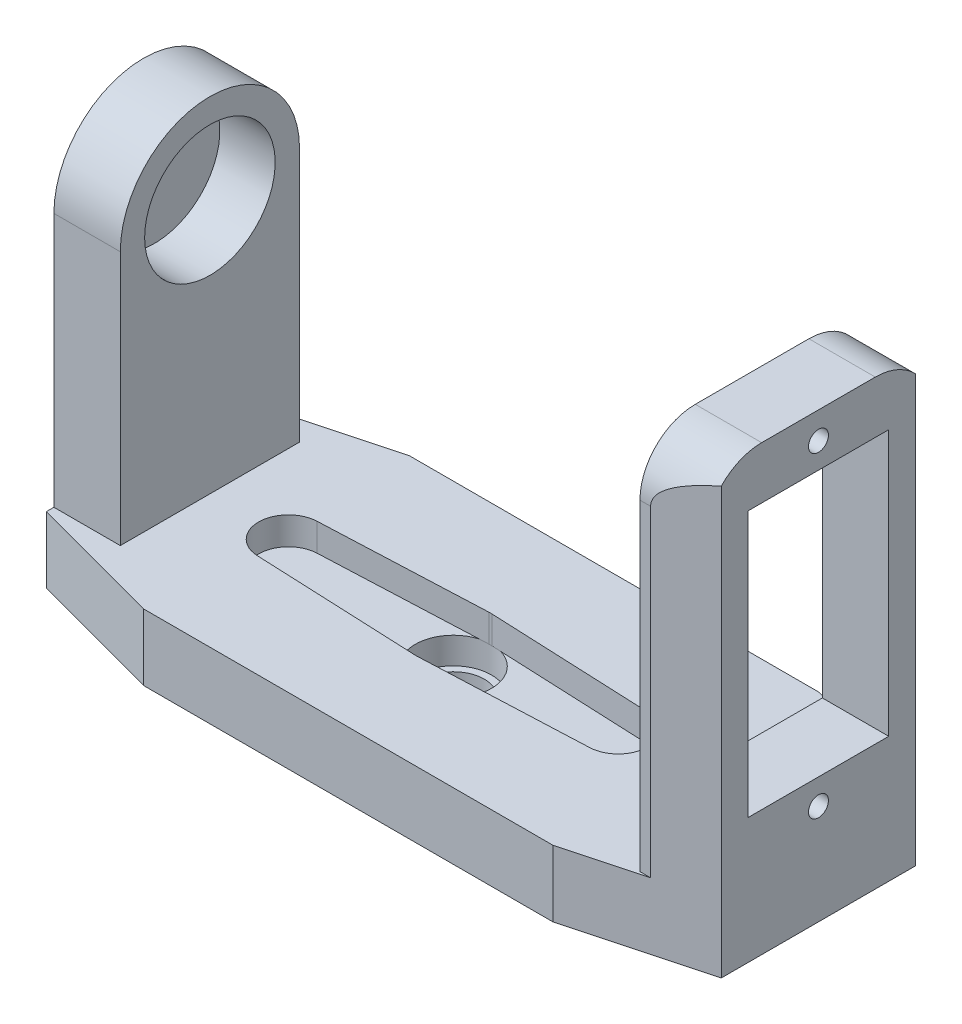
SolidWorks part; units mm, degrees
ref_plane "前视基准面" through (0, 0, 0) normal (0, 0, 1) x (1, 0, 0)
ref_plane "上视基准面" through (0, 0, 0) normal (0, 1, 0) x (1, 0, 0)
ref_plane "右视基准面" through (0, 0, 0) normal (1, 0, 0) x (0, 0, -1)
sketch "草图1" plane through (0, 0, 0) normal (0, 1, 0) x (1, 0, 0)
  line L0 (0, 0) -> (2.5, 0) construction
  line L1 (33, -12) -> (-28, -12)
  line L2 (33, -12) -> (33, 12)
  line L3 (33, 12) -> (-28, 12)
  line L4 (-28, -12) -> (-28, 12)
  line L5 (33, -12) -> (-28, 12) construction
  line L6 (33, 12) -> (-28, -12) construction
  point P0 (0, 0)
  dimension "D1" = 28
  dimension "D2" = 33
  dimension "D3" = 24
extrude "凸台-拉伸1" add sketch "草图1" along normal blind 6
sketch "草图2" plane through (-28, 0, 0) normal (-1, 0, 0) x (0, 0, 1)
  line L0 (-12, 6) -> (12, 6) construction
  line L1 (8.0991, 37.0991) -> (-8.0991, 37.0991)
  line L2 (8.0991, 37.0991) -> (8.0991, 6)
  line L3 (8.0991, 6) -> (-8.0991, 6)
  line L4 (-8.0991, 37.0991) -> (-8.0991, 6)
  line L5 (8.0991, 37.0991) -> (-8.0991, 6) construction
  line L6 (8.0991, 6) -> (-8.0991, 37.0991) construction
  line L7 (0, 21.5496) -> (0, 6) construction
  circle A0 centre (0, 29) radius 5.9
  circle A1 centre (0, 29) radius 8.0991 construction
  point P0 (0, 21.5496)
  dimension "D2" = 11.8
  dimension "D1" = 23
extrude "凸台-拉伸2" add sketch "草图2" against normal blind 6
sketch "草图8" plane through (-28, 0, 0) normal (-1, 0, 0) x (0, 0, 1)
  circle A1 centre (0, 29) radius 5.9 construction
  circle A2 centre (0, 29) radius 5.9
extrude "凸台-拉伸4" add sketch "草图8" against normal blind 1
fillet "圆角1" 2 edges at (-25, 37.0991, -8.0991) (-25, 37.0991, 8.0991) type full round first side face at (-25, 21.5496, -8.0991) second side face at (-25, 21.5496, 8.0991) middle face at (-25, 37.0991, 0)
sketch "草图3" plane through (33, 0, 0) normal (1, 0, 0) x (0, 0, -1)
  line L0 (0, 23.35) -> (18.2252, 23.35) construction
  line L1 (10.134, 40.0752) -> (-10.134, 40.0752)
  line L2 (10.134, 40.0752) -> (10.134, 6)
  line L3 (10.134, 6) -> (-10.134, 6)
  line L4 (-10.134, 40.0752) -> (-10.134, 6)
  line L5 (10.134, 40.0752) -> (-10.134, 6) construction
  line L6 (10.134, 6) -> (-10.134, 40.0752) construction
  line L7 (0, 23.35) -> (0, 0) construction
  line L8 (6.35, 35.35) -> (-6.35, 35.35)
  line L9 (6.35, 35.35) -> (6.35, 11.35)
  line L10 (6.35, 11.35) -> (-6.35, 11.35)
  line L11 (-6.35, 35.35) -> (-6.35, 11.35)
  line L12 (6.35, 35.35) -> (-6.35, 11.35) construction
  line L13 (6.35, 11.35) -> (-6.35, 35.35) construction
  line L17 (-12, 6) -> (12, 6) construction
  circle A0 centre (0, 29) radius 5.9 construction
  circle A1 centre (0, 29) radius 5.9 construction
  circle A2 centre (0, 9.05) radius 0.9
  circle A3 centre (0, 37.65) radius 0.9
  circle A4 centre (0, 29) radius 6.35 construction
  point P0 (0, 23.0376)
  point P7 (0, 23.35)
  dimension "D5" = 1.8
  dimension "D1" = 24
  dimension "D2" = 12.7
  dimension "D4" = 14.3
extrude "凸台-拉伸3" add sketch "草图3" against normal blind 6
fillet "圆角2" radius 5 2 edges at (30, 40.0752, 10.134) (30, 40.0752, -10.134)
sketch "草图4" plane through (-24, 6, 6) normal (0, -1, 0) x (-1, 0, 0)
  line L0 (-24, 6) -> (-9.0984, 6) construction
  line L1 (-8.998, 3.7022) -> (-23.8713, 3.0528) construction
  line L2 (-23.8713, 8.9472) -> (-8.998, 8.2978) construction
  line L3 (-23.8539, 9.3468) -> (-8.9806, 8.6974)
  line L4 (-8.9806, 3.3026) -> (-23.8539, 2.6532)
  arc A0 (-23.8713, 8.9472) -> (-23.8713, 3.0528) centre (-24, 6) ccw construction
  arc A1 (-8.998, 3.7022) -> (-8.998, 8.2978) centre (-9.0984, 6) ccw construction
  arc A2 (-8.9806, 3.3026) -> (-8.9806, 8.6974) centre (-9.0984, 6) ccw
  arc A3 (-23.8539, 9.3468) -> (-23.8539, 2.6532) centre (-24, 6) ccw
  dimension "D1" = 5.9
  dimension "D2" = 4.6
  dimension "D3" = 5
  dimension "D5" = 0.4
extrude "切除-拉伸1" cut sketch "草图4" along normal blind 2.5
mirror "镜向1" about plane through (0, 0, 0) normal (1, 0, 0) of "切除-拉伸1"
sketch "草图5" plane through (0, 3.5, 0) normal (0, 1, 0) x (1, 0, 0)
  circle A0 centre (0, 0) radius 3.45
extrude "切除-拉伸2" cut sketch "草图5" against normal blind 2.4
chamfer "倒角1" distance 12 angle 15 4 edges at (33, 3, -12) (33, 3, 12) (-28, 3, 12) (-28, 3, -12) first distance on face at (2.5, 3, -12) first distance on face at (2.5, 3, 12)
sketch "草图6" plane through (0, 1.1, 0) normal (0, 1, 0) x (1, 0, 0)
  circle A0 centre (0, 0) radius 2.8
  dimension "D1" = 5.6
extrude "切除-拉伸3" cut sketch "草图6" against normal through all
